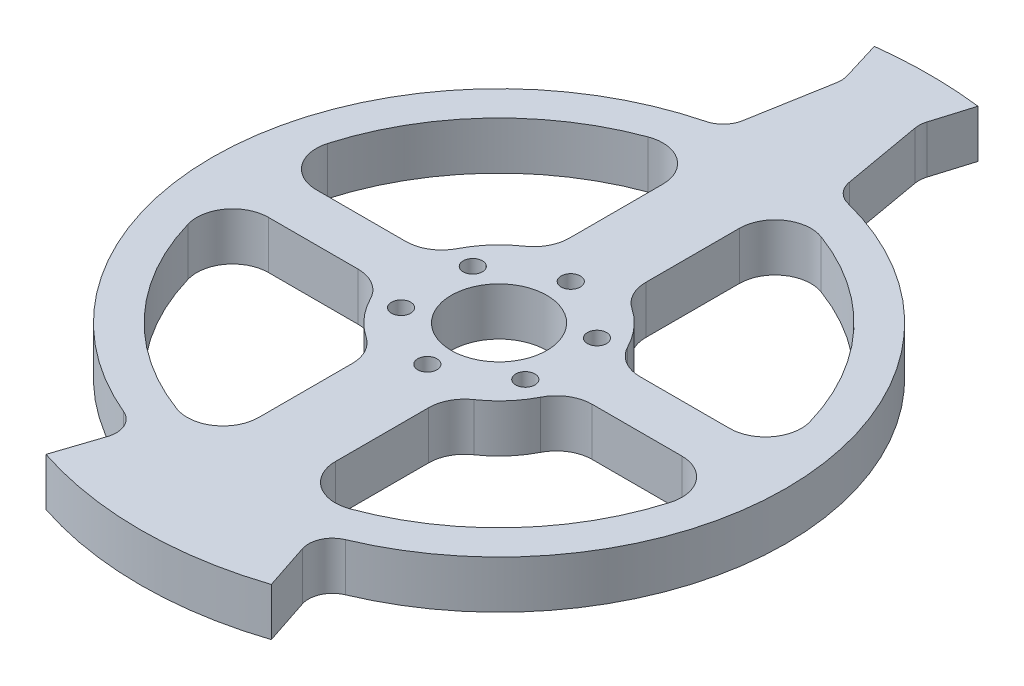
SolidWorks part; units mm, degrees
material "AISI Type A2 Tool Steel"
ref_plane "Front Plane" through (0, 0, 0) normal (0, 0, 1) x (1, 0, 0)
ref_plane "Top Plane" through (0, 0, 0) normal (0, 1, 0) x (1, 0, 0)
ref_plane "Right Plane" through (0, 0, 0) normal (1, 0, 0) x (0, 0, -1)
other "Center of Mass"
other "Bounding Box"
ref_plane "Default Plane" through (0, 2.286, 19.05) normal (0, -1, 0) x (-1, 0, 0)
sketch "Sketch1" plane through (0, 0, 0) normal (0, 1, 0) x (1, 0, 0)
  circle A0 centre (0, 0) radius 114.3 construction
  circle A1 centre (0, 0) radius 76.2
  circle A2 centre (0, 0) radius 12.7
  dimension "D1" = 228.6
  dimension "D2" = 152.4
  dimension "D3" = 25.4
extrude "Boss-Extrude1" add sketch "Sketch1" along normal mid plane 12.7
sketch "Sketch2" plane through (0, 6.35, 0) normal (0, 1, 0) x (1, 0, 0)
  line L0 (-10.16, 101.6) -> (-14.898, 74.7294)
  line L1 (14.898, 74.7294) -> (10.16, 101.6)
  line L2 (10.16, 101.6) -> (13.77, 113.4675)
  line L3 (-10.16, 101.6) -> (-13.77, 113.4675)
  line L4 (0, 0) -> (0, 114.3) construction
  line L5 (-10.16, 101.6) -> (0, 101.6) construction
  line L6 (0, 101.6) -> (10.16, 101.6) construction
  line L7 (-13.77, 113.4675) -> (0, 0) construction
  circle A0 centre (0, 0) radius 114.3 construction
  circle A1 centre (0, 0) radius 114.3 construction
  arc A2 (-13.77, 113.4675) -> (13.77, 113.4675) centre (0, 0) cw
  circle A5 centre (0, 0) radius 76.2
  arc A6 (14.898, 74.7294) -> (-14.898, 74.7294) centre (0, 0) ccw
  arc A7 (-14.898, 74.7294) -> (14.898, 74.7294) centre (0, 0) ccw construction
  dimension "D3" = 10
  dimension "D4" = 12.7
  dimension "D5" = 10
  dimension "D6" = 10.16
  dimension "D2" = 0
extrude "Boss-Extrude2" add sketch "Sketch2" against normal through all
sketch "Sketch3" plane through (0, 6.35, 0) normal (0, 1, 0) x (1, 0, 0)
  line L0 (-29.9275, -90.4262) -> (-23.942, -72.341)
  line L1 (23.942, -72.341) -> (29.9275, -90.4262)
  line L2 (0, -76.2) -> (0, -95.25) construction
  line L3 (0, -95.25) -> (0, -114.3) construction
  line L4 (-23.942, -72.341) -> (0, 0) construction
  line L5 (0, 0) -> (23.942, -72.341) construction
  arc A0 (-29.9275, -90.4262) -> (29.9275, -90.4262) centre (0, 0) ccw
  circle A1 centre (0, 0) radius 76.2 construction
  circle A2 centre (0, 0) radius 114.3 construction
  arc A3 (-23.942, -72.341) -> (23.942, -72.341) centre (0, 0) ccw
  point P13 (0, -95.25)
  dimension "D1" = 36.625
extrude "Boss-Extrude3" add sketch "Sketch3" against normal through all
sketch "Sketch4" plane through (0, 6.35, 0) normal (0, 1, 0) x (1, 0, 0)
  line L0 (0, 0) -> (-76.2, 0) construction
  line L1 (-66.3719, -6.35) -> (-24.5934, -6.35)
  line L4 (-10.16, -65.8964) -> (-10.16, -23.2795)
  line L8 (0, -95.25) -> (0, 0) construction
  arc A0 (-10.16, -23.2795) -> (-24.5934, -6.35) centre (0, 0) cw
  arc A1 (-10.16, -65.8964) -> (-66.3719, -6.35) centre (0, 0) cw
  circle A2 centre (0, 0) radius 76.2 construction
  arc A5 (-29.9275, -90.4262) -> (29.9275, -90.4262) centre (0, 0) ccw construction
  arc A6 (-14.898, 74.7294) -> (-23.942, -72.341) centre (0, 0) ccw construction
  dimension "D1" = 9.525
  dimension "D2" = 25.4
  dimension "D3" = 10.16
  dimension "D4" = 6.35
extrude "Cut-Extrude1" cut sketch "Sketch4" against normal through all
mirror "Mirror1" about plane through (0, 0, 0) normal (1, 0, 0) of "Cut-Extrude1"
mirror "Mirror2" about plane through (0, 0, 0) normal (0, 0, 1) of "Mirror1"
sketch "Sketch5" plane through (0, 6.35, 0) normal (0, 1, 0) x (1, 0, 0)
  line L0 (0, 19.05) -> (0, 0) construction
  circle A0 centre (0, 19.05) radius 2.5527
  dimension "D2" = 5.1054
  dimension "D1" = 19.05
extrude "Cut-Extrude2" cut sketch "Sketch5" against normal through all
pattern_circular "CirPattern1" count 6 over 360 about axis through (0, 6.35, 0) along (0, -1, 0) of "Cut-Extrude2"
fillet "Fillet1" radius 6.35 6 edges at (-23.942, 0, 72.341) (23.942, 0, 72.341) (14.898, 0, -74.7294) (10.16, 0, -101.6) (-14.898, 0, -74.7294) (-10.16, 0, -101.6)
fillet "Fillet4" radius 9.525 8 edges at (-10.16, 0, -65.8964) (-66.3719, 0, -6.35) (-66.3719, 0, 6.35) (-10.16, 0, 65.8964) (10.16, 0, 65.8964) (66.3719, 0, 6.35) (66.3719, 0, -6.35) (10.16, 0, -65.8964)
fillet "Fillet5" radius 9.525 8 edges at (-24.5934, 0, -6.35) (-10.16, 0, -23.2795) (10.16, 0, -23.2795) (24.5934, 0, -6.35) (10.16, 0, 23.2795) (24.5934, 0, 6.35) (-24.5934, 0, 6.35) (-10.16, 0, 23.2795)
equation "\"Unit Measure\"= \"BoundingVolume\" / \"Thickness\"'in^2"
